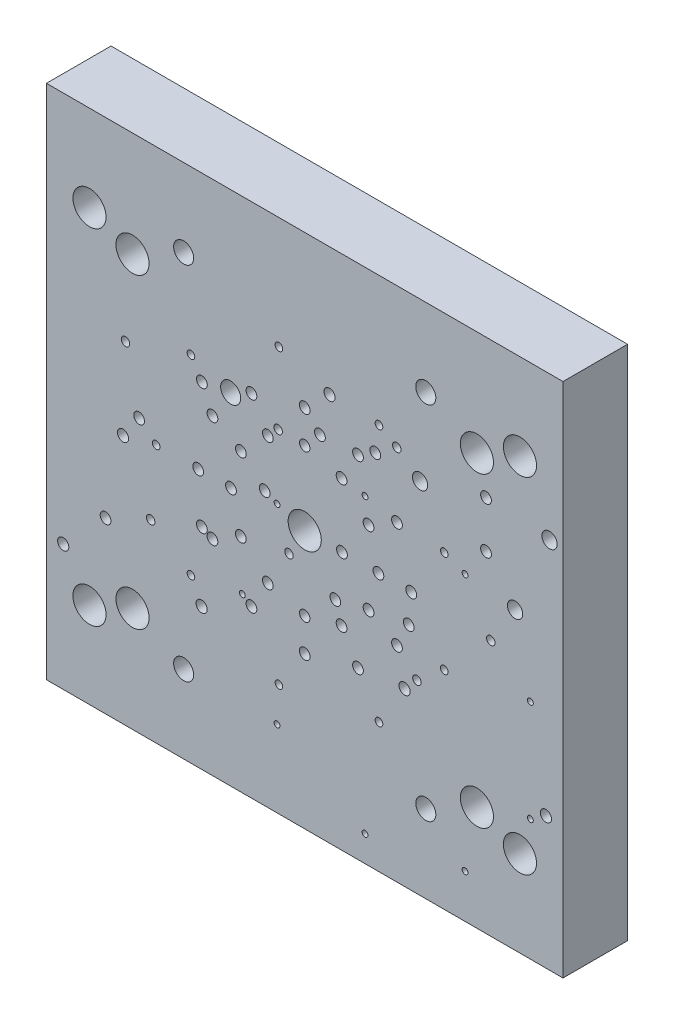
SolidWorks part; units mm, degrees
ref_plane "Front Plane" through (0, 0, 0) normal (0, 0, 1) x (1, 0, 0)
ref_plane "Top Plane" through (0, 0, 0) normal (0, 1, 0) x (1, 0, 0)
ref_plane "Right Plane" through (0, 0, 0) normal (1, 0, 0) x (0, 0, -1)
sketch "Sketch1" plane through (0, 0, 0) normal (0, 0, 1) x (1, 0, 0)
  line L1 (-152.4, 152.4) -> (152.4, 152.4)
  line L2 (-152.4, 152.4) -> (-152.4, -152.4)
  line L3 (-152.4, -152.4) -> (152.4, -152.4)
  line L4 (152.4, 152.4) -> (152.4, -152.4)
  line L5 (-152.4, 152.4) -> (152.4, -152.4) construction
  line L6 (-152.4, -152.4) -> (152.4, 152.4) construction
  point P0 (0, 0)
  dimension "D1" = 304.8
  dimension "D2" = 304.8
extrude "Boss-Extrude1" add sketch "Sketch1" along normal blind 38.1
sketch "Sketch2" plane through (0, 0, 38.1) normal (0, 0, 1) x (1, 0, 0)
  line L0 (-152.4, 0) -> (152.4, 0) construction
  line L5 (-152.4, 152.4) -> (-152.4, -152.4) construction
  line L6 (152.4, -152.4) -> (152.4, 152.4) construction
  line L7 (-152.4, -101.6) -> (152.4, -101.6) construction
  line L8 (-152.4, 101.6) -> (152.4, 101.6) construction
  line L9 (0, 101.6) -> (0, -101.6) construction
  line L10 (127, 101.6) -> (127, -101.6) construction
  line L11 (-127, 101.6) -> (-127, -101.6) construction
  circle A0 centre (-127, 101.6) radius 6.5151
  circle A1 centre (127, 101.6) radius 6.5151
  circle A2 centre (127, -101.6) radius 6.5151
  circle A3 centre (-127, -101.6) radius 6.5151
  circle A4 centre (0, 0) radius 6.5151
  dimension "D5" = 13.0302
  dimension "D1" = 101.6
  dimension "D2" = 101.6
  dimension "D3" = 127
  dimension "D4" = 127
extrude "HAAS T-Slot Holes" cut sketch "Sketch2" against normal through all
sketch "Sketch3" plane through (0, 0, 38.1) normal (0, 0, 1) x (1, 0, 0)
  circle A0 centre (-127, 101.6) radius 9.779
  circle A1 centre (127, 101.6) radius 9.779
  circle A2 centre (0, 0) radius 9.779
  circle A3 centre (127, -101.6) radius 9.779
  circle A4 centre (-127, -101.6) radius 9.779
  dimension "D1" = 19.558
extrude "HAAS Counter Bores" cut sketch "Sketch3" against normal offset from surface (22.225 mm away) 15.875 contours A0 | A1 | A2 | A3 | A4 up to face at (6.5151, 0, 0)
sketch "Sketch4" plane through (0, 0, 38.1) normal (0, 0, 1) x (1, 0, 0)
  line L0 (-127, 90.4875) -> (127, 90.4875) construction
  line L1 (-127, 30.1625) -> (127, 30.1625) construction
  line L2 (-127, 30.1625) -> (-127, -30.1625) construction
  line L3 (-127, -30.1625) -> (127, -30.1625) construction
  line L4 (127, 30.1625) -> (127, -30.1625) construction
  line L5 (-127, 30.1625) -> (127, -30.1625) construction
  line L6 (-127, -30.1625) -> (127, 30.1625) construction
  line L7 (-127, -90.4875) -> (127, -90.4875) construction
  line L8 (-101.6, 90.4875) -> (-101.6, 84.1375) construction
  line L9 (-101.6, -90.4875) -> (-101.6, -84.1375) construction
  line L10 (101.6, -90.4875) -> (101.6, -84.1375) construction
  line L11 (101.6, 90.4875) -> (101.6, 84.1375) construction
  circle A0 centre (-101.6, 90.4875) radius 6.5151
  circle A1 centre (101.6, 90.4875) radius 6.5151
  circle A2 centre (-101.6, -90.4875) radius 6.5151
  circle A3 centre (101.6, -90.4875) radius 6.5151
  point P0 (0, 0)
  dimension "D9" = 13.0302
  dimension "D1" = 60.325
  dimension "D2" = 254
  dimension "D5" = 203.2
  dimension "D6" = 25.4
  dimension "D7" = 203.2
  dimension "D8" = 6.35
  dimension "D3" = 60.325
  dimension "D4" = 60.325
extrude "Tormach T-Slot Holes" cut sketch "Sketch4" against normal through all
sketch "Sketch5" plane through (0, 0, 38.1) normal (0, 0, 1) x (1, 0, 0)
  circle A0 centre (-101.6, 90.4875) radius 9.779
  circle A1 centre (101.6, 90.4875) radius 9.779
  circle A2 centre (101.6, -90.4875) radius 9.779
  circle A3 centre (-101.6, -90.4875) radius 9.779
  dimension "D1" = 19.558
extrude "Tormach Counter bores" cut sketch "Sketch5" against normal up to surface (22.225 mm away) up to face at (-117.221, 101.6, 15.875)
sketch "Sketch6" plane through (0, 0, 38.1) normal (0, 0, 1) x (1, 0, 0)
  circle A0 centre (0, 0) radius 43.5 construction
  circle A1 centre (0, 43.5) radius 3.0734
  circle A2 centre (0, -43.5) radius 3.0734
  dimension "D1" = 87.0001
  dimension "D2" = 6.1468
extrude "Sprocket Locating Holes" cut sketch "Sketch6" against normal blind 6.35
sketch "Sketch7" plane through (0, 0, 38.1) normal (0, 0, 1) x (1, 0, 0)
  circle A0 centre (0, 0) radius 43.5 construction
  circle A2 centre (43.5, 0) radius 3.175
  circle A4 centre (37.6721, -21.75) radius 3.175
  circle A5 centre (21.75, -37.6721) radius 3.175
  circle A6 centre (0, -43.5) radius 3.175 [skipped]
  circle A7 centre (-21.75, -37.6721) radius 3.175
  circle A8 centre (-37.6721, -21.75) radius 3.175
  circle A9 centre (-43.5, 0) radius 3.175
  circle A10 centre (-37.6721, 21.75) radius 3.175
  circle A11 centre (-21.75, 37.6721) radius 3.175
  circle A12 centre (0, 43.5) radius 3.175 [skipped]
  circle A13 centre (21.75, 37.6721) radius 3.175
  circle A14 centre (37.6721, 21.75) radius 3.175
  point P31 (0, 0)
  dimension "D1" = 87.0001
  dimension "D2" = 6.35
  dimension "D3" = 12
extrude "Sprocket Mounting clearance holes" cut sketch "Sketch7" against normal blind 9.525
sketch "Sketch8" plane through (0, 0, 38.1) normal (0, 0, 1) x (1, 0, 0)
  line L1 (-71.4375, 106.4641) -> (71.4375, 106.4641) construction
  line L2 (-71.4375, 106.4641) -> (-71.4375, -106.4641) construction
  line L3 (-71.4375, -106.4641) -> (71.4375, -106.4641) construction
  line L4 (71.4375, 106.4641) -> (71.4375, -106.4641) construction
  line L5 (-71.4375, 106.4641) -> (71.4375, -106.4641) construction
  line L6 (-71.4375, -106.4641) -> (71.4375, 106.4641) construction
  circle A0 centre (-71.4375, 106.4641) radius 5.9182
  circle A1 centre (71.4375, 106.4641) radius 5.9182
  circle A2 centre (71.4375, -106.4641) radius 5.9182
  circle A3 centre (-71.4375, -106.4641) radius 5.9182
  point P0 (0, 0)
  dimension "D3" = 11.8364
  dimension "D1" = 142.875
  dimension "D2" = 212.9282
extrude "1/2-13 Tapped Holes" cut sketch "Sketch8" against normal blind 19.05
sketch "Sketch9" plane through (0, 0, 38.1) normal (0, 0, 1) x (1, 0, 0)
  circle A0 centre (-117.5189, -52.2876) radius 3.175
  circle A1 centre (-60.6634, -28.4101) radius 3.175
  circle A2 centre (-60.6634, 45.677) radius 3.175
  circle A3 centre (-23.6198, 8.6335) radius 3.175
  circle A4 centre (-97.707, 8.6335) radius 3.175
  circle A5 centre (18.0623, -26.1797) radius 3.175
  circle A6 centre (21.9762, 0) radius 3.175
  circle A7 centre (61.3833, -17.3739) radius 3.175
  circle A8 centre (106.976, 70.3959) radius 3.175
  circle A9 centre (106.976, 42.9004) radius 3.175
  circle A10 centre (144.4539, 67.4373) radius 4.5
  circle A11 centre (124.1092, 21.6131) radius 4.5
  circle A12 centre (68.0681, 59.3279) radius 4.5
  circle A13 centre (58.9353, -51.2652) radius 3.3
  circle A14 centre (-142.4923, -78.095) radius 3.3
  circle A15 centre (-105.7351, 43.7713) radius 2.5
  circle A16 centre (-90.8975, -39.8642) radius 2.5
  circle A17 centre (-9.2711, -16.3656) radius 2.5
  circle A18 centre (-15.6655, 43.8657) radius 2.5
  circle A20 centre (14.6267, 76.8405) radius 3.3
  circle A21 centre (8.9855, 53.4682) radius 3.175
  circle A22 centre (41.6559, 60.6579) radius 3.175
extrude "SSB Holes" cut sketch "Sketch9" against normal blind 19.05
ref_axis "Axis1" through (0, 0, 0) along (0, 0, 1)
sketch "Sketch10" plane through (0, 0, 38.1) normal (0, 0, 1) x (1, 0, 0)
  circle A0 centre (0, 0) radius 62.865 construction
  circle A1 centre (0, 62.865) radius 3.175
  circle A13 centre (31.4325, 54.4427) radius 3.175
  circle A14 centre (54.4427, 31.4325) radius 3.175
  circle A15 centre (62.865, 0) radius 3.175
  circle A16 centre (54.4427, -31.4325) radius 3.175
  circle A17 centre (31.4325, -54.4427) radius 3.175
  circle A18 centre (0, -62.865) radius 3.175
  circle A19 centre (-31.4325, -54.4427) radius 3.175
  circle A20 centre (-54.4427, -31.4325) radius 3.175
  circle A21 centre (-62.865, 0) radius 3.175
  circle A22 centre (-54.4427, 31.4325) radius 3.175
  circle A23 centre (-31.4325, 54.4427) radius 3.175
  point P30 (0, 0)
  point P56 (0, 0)
  dimension "D1" = 125.73
  dimension "D2" = 6.35
  dimension "D4" = 12
extrude "Sprocket Countersunk Holes" cut sketch "Sketch10" against normal blind 19.05
sketch "Sketch12" plane through (0, 0, 38.1) normal (0, 0, 1) x (1, 0, 0)
  circle A0 centre (-107.2144, -4.9977) radius 3.3
  circle A1 centre (-60.8212, -69.1392) radius 3.3
  circle A2 centre (142.3129, -74.567) radius 3.3
  circle A4 centre (54.3307, 69.7186) radius 2.4964
  circle A5 centre (109.7823, -1.2607) radius 2.5
  circle A6 centre (66.2094, -43.3332) radius 2.5
  circle A7 centre (-43.6886, 48.7489) radius 5.9182
  circle A8 centre (-71.4375, 106.4641) radius 5.9182 construction
extrude "DSB Holes" cut sketch "Sketch12" against normal blind 19.05
sketch "Brake Rotor Toe Clamp Holes" plane through (0, 0, 38.1) normal (0, 0, 1) x (1, 0, 0)
  line L0 (-74.6653, 106.6331) -> (74.6653, -106.6331) construction
  line L1 (74.6653, 106.6331) -> (-74.6653, -106.6331) construction
  line L6 (0, 0) -> (192.0367, 0) construction
  line L7 (0, 0) -> (-160.9096, 0) construction
  line L8 (0, 0) -> (0, 219.8313) construction
  line L9 (0, 0) -> (-215.8918, 38.0675) construction
  circle A0 centre (0, 0) radius 130.175 construction
  circle A10 centre (-87.63, 0) radius 2.3813 construction
  circle A12 centre (-74.93, 0) radius 2.3813 construction
  circle A13 centre (-80.0452, 14.1141) radius 2.3813
  circle A14 centre (-70.4112, 25.6276) radius 2.3812 construction
  circle A15 centre (-70.3905, 40.64) radius 2.3812 construction
  circle A16 centre (-82.3453, 29.9712) radius 2.3812 construction
  circle A17 centre (-57.3997, 48.1641) radius 2.3813 construction
  circle A18 centre (-52.2458, 62.2641) radius 2.3812
  circle A19 centre (-67.1285, 56.3275) radius 2.3812 construction
  circle A20 centre (-37.465, 64.8913) radius 2.3813 construction
  circle A21 centre (-27.7994, 76.3782) radius 2.3813 construction
  circle A22 centre (-43.815, 75.8898) radius 2.3813 construction
  circle A23 centre (-13.0115, 73.7916) radius 2.3813 construction
  circle A24 centre (0, 81.28) radius 2.3813
  circle A25 centre (-15.2168, 86.2987) radius 2.3813 construction
  circle A26 centre (13.0115, 73.7916) radius 2.3812 construction
  circle A27 centre (27.7994, 76.3782) radius 2.3812 construction
  circle A28 centre (15.2168, 86.2987) radius 2.3813 construction
  circle A29 centre (37.465, 64.8913) radius 2.3812 construction
  circle A30 centre (52.2458, 62.2641) radius 2.3813
  circle A31 centre (43.815, 75.8898) radius 2.3812 construction
  circle A32 centre (57.3997, 48.1641) radius 2.3813 construction
  circle A33 centre (70.3905, 40.64) radius 2.3813 construction
  circle A34 centre (67.1285, 56.3275) radius 2.3813 construction
  circle A35 centre (70.4112, 25.6276) radius 2.3813 construction
  circle A36 centre (80.0452, 14.1141) radius 2.3813
  circle A37 centre (82.3453, 29.9712) radius 2.3813 construction
  circle A38 centre (74.93, 0) radius 2.3813 construction
  circle A39 centre (80.0452, -14.1141) radius 2.3813 construction
  circle A40 centre (87.63, 0) radius 2.3813 construction
  circle A41 centre (70.4112, -25.6276) radius 2.3812 construction
  circle A42 centre (70.3905, -40.64) radius 2.3813
  circle A43 centre (82.3453, -29.9712) radius 2.3812 construction
  circle A44 centre (57.3997, -48.1641) radius 2.3813 construction
  circle A45 centre (52.2458, -62.2641) radius 2.3813 construction
  circle A46 centre (67.1285, -56.3275) radius 2.3812 construction
  circle A47 centre (37.465, -64.8913) radius 2.3813 construction
  circle A48 centre (27.7994, -76.3782) radius 2.3813
  circle A49 centre (43.815, -75.8898) radius 2.3813 construction
  circle A50 centre (13.0115, -73.7916) radius 2.3813 construction
  circle A51 centre (0, -81.28) radius 2.3812 construction
  circle A52 centre (15.2168, -86.2987) radius 2.3813 construction
  circle A53 centre (-13.0115, -73.7916) radius 2.3813 construction
  circle A54 centre (-27.7994, -76.3782) radius 2.3813
  circle A55 centre (-15.2168, -86.2987) radius 2.3813 construction
  circle A56 centre (-37.465, -64.8913) radius 2.3813 construction
  circle A57 centre (-52.2458, -62.2641) radius 2.3813 construction
  circle A58 centre (-43.815, -75.8898) radius 2.3812 construction
  circle A59 centre (-57.3997, -48.1641) radius 2.3813 construction
  circle A60 centre (-70.3905, -40.64) radius 2.3813
  circle A61 centre (-67.1285, -56.3275) radius 2.3813 construction
  circle A62 centre (-70.4112, -25.6276) radius 2.3813 construction
  circle A63 centre (-80.0452, -14.1141) radius 2.3813 construction
  circle A64 centre (-82.3453, -29.9712) radius 2.3813 construction
  point P27 (0, 0)
  point P130 (0, 0)
  dimension "D1" = 260.35
  dimension "D17" = 4.7625
  dimension "D18" = 81.28
  dimension "D19" = 18
  dimension "D14" = 4.7625
  dimension "D15" = 4.7625
  dimension "D10" = 55
  dimension "D11" = 55
  dimension "D12" = 87.63
  dimension "D13" = 12.7
  dimension "D16" = 10
hole_wizard "Rotor Clamp Bolts" positions "Sketch15" profile "Sketch16" hole size "M4" standard "AS"
sketch "Sketch15" plane through (0, 0, 38.1) normal (0, 0, 1) x (1, 0, 0)
  point P0 (-87.63, 0)
  point P3 (-67.1285, -56.3275)
  point P6 (-15.2168, -86.2987)
  point P9 (43.815, -75.8898)
  point P12 (82.3453, -29.9712)
  point P15 (82.3453, 29.9712)
  point P18 (43.815, 75.8898)
  point P21 (-15.2168, 86.2987)
  point P24 (-67.1285, 56.3275)
sketch "Sketch16" plane through (-87.63, 0, 38.1) normal (1, 0, 0) x (0, -1, 0)
  line L0 (0, 0) -> (0, 20.4019)
  line L1 (0, 20.4019) -> (2.25, 19.05)
  line L2 (2.25, 19.05) -> (2.25, 0)
  line L5 (2.25, 0) -> (0, 0)
  line L10 (0, 20.4019) -> (-2.25, 19.05) construction
  line L11 (0, -6.35) -> (0, 107.95) construction
  dimension "Hole Dia." = 4.5
  dimension "Hole Depth" = 19.05
  dimension "Drill Angle" = 118
sketch "Sketch17" plane through (0, 0, 38.1) normal (0, 0, 1) x (1, 0, 0)
  line L0 (-152.4, -152.4) -> (152.4, -152.4) construction
  line L3 (152.4, -152.4) -> (-48.9194, -152.4)
  line L6 (-48.9194, 53.8931) -> (152.4, 53.8931)
  line L7 (-48.9194, 53.8931) -> (-48.9194, -152.4)
  line L8 (152.4, 53.8931) -> (152.4, -152.4)
sketch "New Rotor Holes" plane through (0, 0, 38.1) normal (0, 0, 1) x (1, 0, 0)
  circle A0 centre (50.8, -50.8) radius 87.63 construction
  circle A1 centre (-36.83, -50.8) radius 1.7272
  circle A2 centre (-16.3285, -107.1275) radius 1.7272
  circle A3 centre (35.5832, -137.0987) radius 1.7272
  circle A4 centre (94.615, -126.6898) radius 1.7272
  circle A5 centre (133.1453, -80.7712) radius 1.7272
  circle A6 centre (133.1453, -20.8288) radius 1.7272
  circle A7 centre (94.615, 25.0898) radius 1.7272
  circle A8 centre (35.5832, 35.4987) radius 1.7272
  circle A9 centre (-16.3285, 5.5275) radius 1.7272
  point P24 (50.8, -50.8)
  dimension "D3" = 175.26
  dimension "D4" = 3.4544
  dimension "D1" = 50.8
  dimension "D2" = 50.8
  dimension "D5" = 9
extrude "8-32 hole Prep" cut sketch "New Rotor Holes" against normal blind 19.05
equation "\"boltRotor\"=0.75"
equation "\"bolt\"=0.51159"
